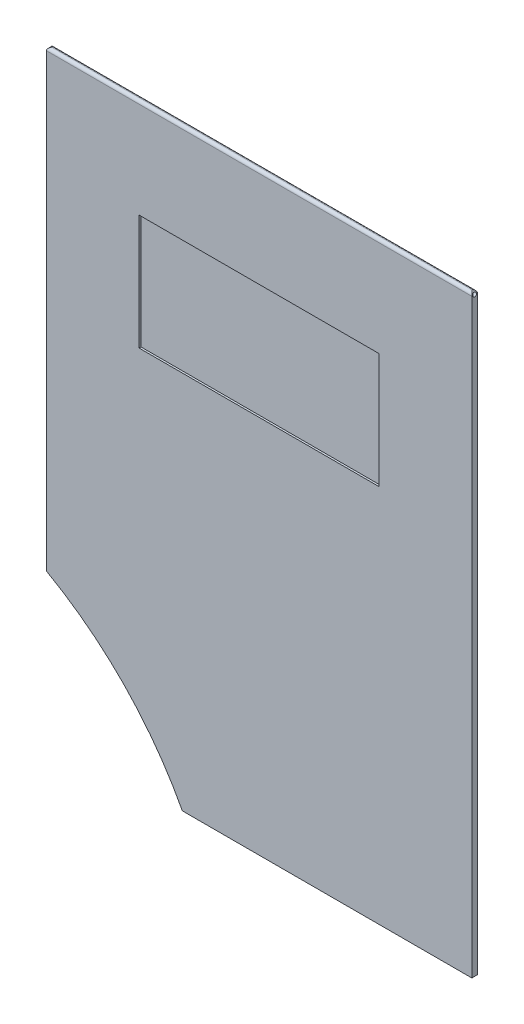
SolidWorks part; units mm, degrees
material "AISI 316 退火不锈钢条 (SS)"
ref_plane "前视基准面" through (0, 0, 0) normal (0, 0, 1) x (1, 0, 0)
ref_plane "上视基准面" through (0, 0, 0) normal (0, 1, 0) x (1, 0, 0)
ref_plane "右视基准面" through (0, 0, 0) normal (1, 0, 0) x (0, 0, -1)
sketch "草图1" plane through (0, 0, 0) normal (0, 0, 1) x (1, 0, 0)
  line L0 (8.5081, 51.0516) -> (-241.4919, 51.0516)
  line L1 (-1091.4919, 451.0516) -> (8.5081, 451.0516)
  line L2 (-1091.4919, 451.0516) -> (-1091.4919, 51.0516)
  line L3 (-1091.4919, 51.0516) -> (8.5081, 51.0516)
  line L4 (8.5081, 451.0516) -> (8.5081, 51.0516)
  line L5 (-241.4919, 51.0516) -> (-241.4919, -18.9484)
  line L6 (-241.4919, -18.9484) -> (-741.4919, -18.9484)
  line L7 (-741.4919, -18.9484) -> (-741.4919, 51.0516)
  line L8 (-741.4919, 51.0516) -> (-1091.4919, 51.0516)
  line L9 (-1091.4919, 51.0516) -> (-653.0919, 51.0516)
  line L11 (-653.0919, 51.0516) -> (-431.4919, 51.0516)
  line L12 (-653.0919, 51.0516) -> (-653.0919, 374.0516)
  line L13 (-653.0919, 374.0516) -> (-431.4919, 374.0516)
  line L14 (-431.4919, 51.0516) -> (-431.4919, 374.0516)
  line L15 (-431.4919, 51.0516) -> (-653.0919, 51.0516)
  line L16 (-431.4919, 51.0516) -> (-431.4919, 65.0516)
  line L17 (-431.4919, 65.0516) -> (-653.0919, 65.0516)
  line L18 (-653.0919, 51.0516) -> (-653.0919, 65.0516)
  circle A0 centre (-741.4919, -18.9484) radius 180
  circle A1 centre (-241.4919, -18.9484) radius 180
  dimension "D6" = 360
  dimension "D7" = 360
  dimension "D1" = 400
  dimension "D2" = 1100
  dimension "D3" = 250
  dimension "D4" = 70
  dimension "D5" = 350
  dimension "D8" = 438.4
  dimension "D9" = 221.6
  dimension "D10" = 323
  dimension "D11" = 14
extrude "凸台-拉伸1" add sketch "草图1" along normal blind 3 contours A0 L17 L14 L13 L12 region at (-538.299, 225.5649, 0)
sketch "草图3" plane through (-431.4919, 0, 0) normal (1, 0, 0) x (0, 0, -1)
  line L0 (-1.5, 374.0516) -> (-1.5, 372.5516)
  line L1 (-3, 374.0516) -> (0, 374.0516) construction
  circle A0 centre (-1.5, 372.5516) radius 1
  dimension "D2" = 2
  dimension "D1" = 1.5
extrude "切除-拉伸1" cut sketch "草图3" against normal through all contours A0 region at (-431.4919, 371.8645, 2.1871)
fillet "圆角1" radius 1.5 4 edges at (-431.4919, 374.0516, 1.5) (-542.2919, 374.0516, 3) (-653.0919, 374.0516, 1.5) (-542.2919, 374.0516, 0)
sketch "草图4" plane through (0, 0, 0) normal (0, 0, -1) x (-1, 0, 0)
  line L0 (653.0919, 137.8491) -> (653.0919, 372.5516) construction
  line L1 (431.4919, 372.5516) -> (653.0919, 372.5516)
  line L2 (431.4919, 372.5516) -> (431.4919, 212.5516)
  line L4 (653.0919, 372.5516) -> (653.0919, 212.5516)
  line L8 (479.7919, 322.5516) -> (604.7919, 322.5516)
  line L9 (479.7919, 322.5516) -> (479.7919, 262.5516)
  line L10 (479.7919, 262.5516) -> (604.7919, 262.5516)
  line L11 (604.7919, 322.5516) -> (604.7919, 262.5516)
  line L12 (479.7919, 322.5516) -> (604.7919, 262.5516) construction
  line L13 (479.7919, 262.5516) -> (604.7919, 322.5516) construction
  point P7 (542.2919, 292.5516)
extrude "切除-拉伸2" cut sketch "草图4" against normal blind 1 contours L11 L8 L9 L10 region at (-542.2919, 292.5516, 0)
sketch "草图5" plane through (0, 0, 3) normal (0, 0, 1) x (1, 0, 0)
  line L0 (-431.4919, 65.0516) -> (-431.4919, 372.5516) construction
  line L1 (-653.0919, 372.5516) -> (-431.4919, 372.5516)
  line L2 (-653.0919, 372.5516) -> (-653.0919, 212.5516)
  line L3 (-653.0919, 212.5516) -> (-431.4919, 212.5516)
  line L4 (-431.4919, 372.5516) -> (-431.4919, 212.5516)
  line L5 (-653.0919, 372.5516) -> (-431.4919, 212.5516)
  line L6 (-653.0919, 212.5516) -> (-431.4919, 372.5516)
  line L8 (-604.7919, 262.5516) -> (-479.7919, 262.5516)
  line L9 (-604.7919, 262.5516) -> (-604.7919, 322.5516)
  line L10 (-604.7919, 322.5516) -> (-479.7919, 322.5516)
  line L11 (-479.7919, 262.5516) -> (-479.7919, 322.5516)
  line L12 (-604.7919, 262.5516) -> (-479.7919, 322.5516) construction
  line L13 (-604.7919, 322.5516) -> (-479.7919, 262.5516) construction
  point P7 (-542.2919, 292.5516)
  dimension "D1" = 160
  dimension "D2" = 125
  dimension "D3" = 60
extrude "切除-拉伸3" cut sketch "草图5" against normal blind 1 contours L8 L11 L10 L6 L5 | L10 L5 L6 | L10 L9 L8 L6 L5 | L6 L8 L5 region at (-542.2919, 312.5516, 3) region at (-582.2054, 292.5516, 3) region at (-502.3784, 292.5516, 3) region at (-542.2919, 272.5516, 3)
